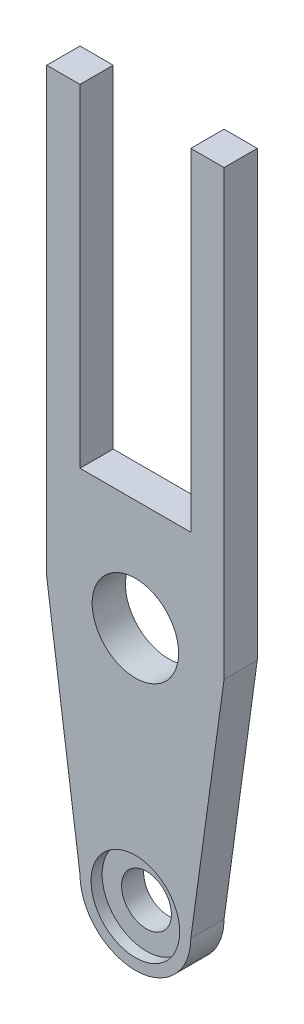
SolidWorks part; units mm, degrees
ref_plane "前视基准面" through (0, 0, 0) normal (0, 0, 1) x (1, 0, 0)
ref_plane "上视基准面" through (0, 0, 0) normal (0, 1, 0) x (1, 0, 0)
ref_plane "右视基准面" through (0, 0, 0) normal (1, 0, 0) x (0, 0, -1)
sketch "草图4" plane through (0, 0, 0) normal (0, 0, 1) x (1, 0, 0)
  line L6 (-5, 30) -> (-5, 10)
  line L8 (-8, 30) -> (-8, 0)
  line L9 (-8, 0) -> (-5, -21.75)
  line L11 (8, 30) -> (8, 0)
  line L12 (8, 0) -> (5, -21.75)
  line L14 (5, 25) -> (5, 30)
  line L16 (-5, 10) -> (5, 10)
  line L17 (5, 10) -> (5, 25)
  line L18 (-5, 30) -> (-5, 40)
  line L19 (-5, 40) -> (-8, 40)
  line L20 (-8, 40) -> (-8, 30)
  line L21 (5, 30) -> (5, 40)
  line L22 (5, 40) -> (8, 40)
  line L23 (8, 40) -> (8, 30)
  arc A4 (-5, -21.75) -> (5, -21.75) centre (0, -21.75) ccw
  circle A5 centre (0, 0) radius 3.9
extrude "凸台-拉伸1" add sketch "草图4" along normal blind 3
hole_wizard "M4 六角凹头盖的柱孔1" positions "3D草图1" profile "草图5" counterbore size "M4" standard "BSI" end condition through all
sketch3d "3D草图1"
  line L0 (0, -21.75, 3) -> (0, -21.75, 0) construction
  point P0 (0, -21.75, 3)
sketch "草图5" plane through (0, -21.75, 3) normal (1, 0, 0) x (0, -1, 0)
  line L0 (0, 0) -> (0, 3)
  line L1 (0, 3) -> (2.25, 3)
  line L3 (2.25, 3) -> (2.25, 1)
  line L4 (2.25, 1) -> (4, 1)
  line L5 (4, 1) -> (4, 0)
  line L7 (4, 0) -> (0, 0)
  line L11 (0, -6.35) -> (0, 107.95) construction
  dimension "通孔孔直径" = 4.5
  dimension "通孔孔深度" = 3
  dimension "柱形沉头孔直径" = 8
  dimension "柱形沉头孔深度" = 1
